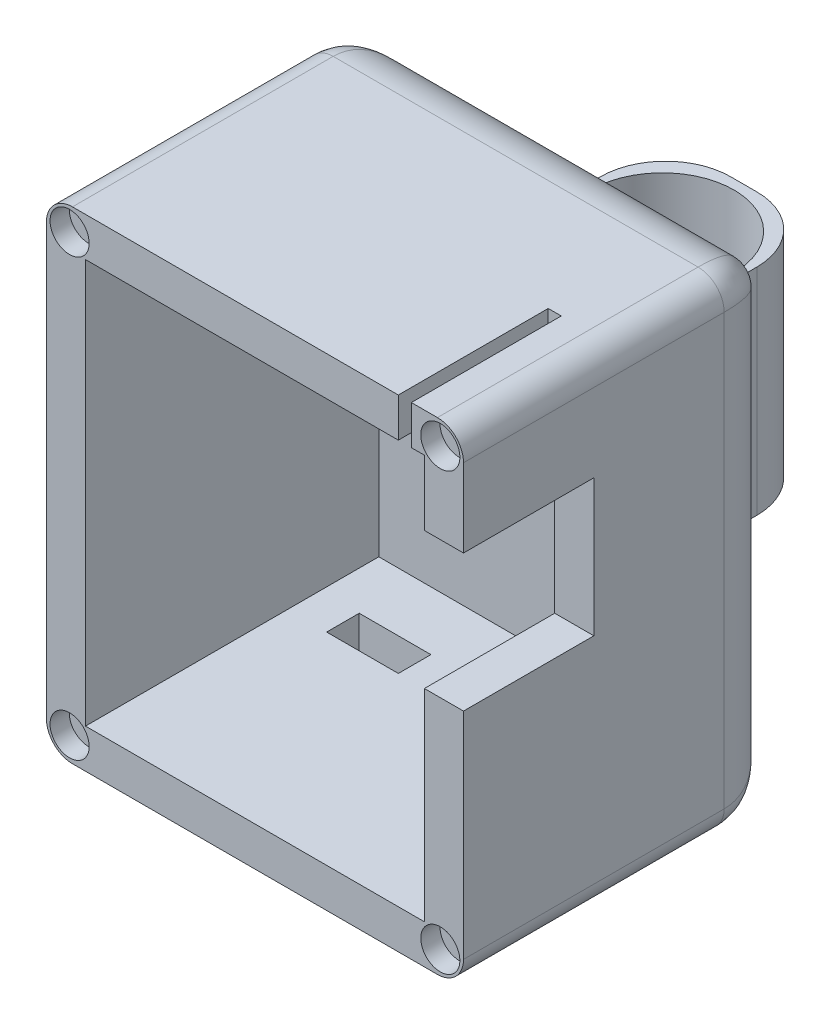
SolidWorks part; units mm, degrees
ref_plane "정면" through (0, 0, 0) normal (0, 0, 1) x (1, 0, 0)
ref_plane "윗면" through (0, 0, 0) normal (0, 1, 0) x (1, 0, 0)
ref_plane "우측면" through (0, 0, 0) normal (1, 0, 0) x (0, 0, -1)
sketch "스케치1" plane through (0, 0, 0) normal (0, 0, 1) x (1, 0, 0)
  line L0 (32, 74) -> (32, 0) construction
  line L1 (0, 0) -> (64, 0)
  line L2 (0, 0) -> (0, 74)
  line L3 (0, 74) -> (64, 74)
  line L4 (64, 0) -> (64, 74)
  line L5 (0, 37) -> (64, 37) construction
  line L6 (0, 74) -> (6, 68) construction
  line L7 (6, 6) -> (58, 6)
  line L8 (6, 6) -> (6, 68)
  line L9 (6, 68) -> (58, 68)
  line L10 (58, 6) -> (58, 68)
  line L11 (64, 74) -> (58, 68) construction
  circle A0 centre (3.5212, 70.4788) radius 3
  circle A1 centre (60.4788, 70.4788) radius 3
  circle A2 centre (60.4788, 3.5212) radius 3
  circle A3 centre (3.5212, 3.5212) radius 3
  point P9 (32, 37)
  dimension "D5" = 6
  dimension "D1" = 64
  dimension "D2" = 74
  dimension "D3" = 52
  dimension "D4" = 62
extrude "보스-돌출4" add sketch "스케치1" along normal blind 50 contours L4 L3 L2 L1
ref_plane "평면1" through (64, 74, 50) normal (1, 0, 0) x (0, 0, -1)
sketch "스케치5" plane through (0, 0, 50) normal (0, 0, 1) x (1, 0, 0)
  line L0 (32, 74) -> (32, 0) construction
  line L1 (0, 74) -> (64, 74) construction
  line L2 (0, 0) -> (64, 0) construction
  line L3 (0, 37) -> (64, 37) construction
  line L4 (0, 0) -> (0, 74) construction
  line L5 (64, 0) -> (64, 74) construction
  line L7 (6, 6) -> (58, 6)
  line L8 (6, 6) -> (6, 68)
  line L9 (6, 68) -> (58, 68)
  line L10 (58, 6) -> (58, 68)
  line L11 (32, 68) -> (32, 6) construction
  line L12 (6, 37) -> (58, 37) construction
  point P12 (32, 37)
  dimension "D1" = 52
  dimension "D2" = 62
extrude "컷-돌출1" cut sketch "스케치5" against normal blind 45
sketch "스케치6" plane through (0, 0, 50) normal (0, 0, 1) x (1, 0, 0)
  line L6 (0, 74) -> (6, 68) construction
  circle A0 centre (3.5581, 70.4419) radius 3
  circle A1 centre (60.4419, 70.4419) radius 3
  circle A2 centre (60.4419, 3.5581) radius 3
  circle A3 centre (3.5581, 3.5581) radius 3
  dimension "D1" = 6
extrude "컷-돌출2" cut sketch "스케치6" against normal blind 2.95 contours A3 | A2 | A1 | A0
sketch "스케치7" plane through (0, 0, 50) normal (0, 0, 1) x (1, 0, 0)
  line L0 (64, 74) -> (56, 74) construction
  line L1 (0, 74) -> (64, 74) construction
  line L3 (56, 74) -> (54, 74)
  dimension "D1" = 8
  dimension "D2" = 2
sketch "스케치8" plane through (0, 74, 0) normal (0, 1, 0) x (1, 0, 0)
  line L0 (54, -50) -> (54, -27)
  line L1 (64, -50) -> (56, -50) construction
  line L2 (54, -50) -> (56, -50)
  line L3 (56, -50) -> (54, -50) construction
  line L4 (56, -50) -> (56, -27)
  line L5 (56, -27) -> (54, -27)
  dimension "D1" = 23
extrude "컷-돌출4" cut sketch "스케치8" against normal blind 8 contours L0 L5 L4 L2
sketch "스케치9" plane through (64, 0, 0) normal (1, 0, 0) x (0, 0, -1)
  line L0 (0, 74) -> (-30, 74) construction
  line L2 (-50, 74) -> (0, 74) construction
  line L3 (-30, 74) -> (-30, 58) construction
  line L5 (-50, 0) -> (-50, 74) construction
  line L6 (-30, 58) -> (-50, 58)
  line L7 (-30, 58) -> (-30, 37)
  line L8 (-30, 37) -> (-50, 37)
  line L9 (-50, 58) -> (-50, 37)
  dimension "D1" = 30
  dimension "D2" = 16
extrude "컷-돌출5" cut sketch "스케치9" against normal blind 8 contours L7 L8 L9 L6
sketch "스케치10" plane through (0, 0, 0) normal (0, -1, 0) x (1, 0, 0)
  line L0 (0, 0) -> (12, 0) construction
  line L1 (0, 0) -> (64, 0) construction
  line L2 (12, 0) -> (12, 19) construction
  line L4 (12, 19) -> (23, 19)
  line L5 (12, 19) -> (12, 14)
  line L6 (12, 14) -> (23, 14)
  line L7 (23, 19) -> (23, 14)
  dimension "D1" = 12
  dimension "D2" = 19
  dimension "D3" = 11
  dimension "D4" = 5
extrude "컷-돌출6" cut sketch "스케치10" against normal blind 8
fillet "필렛1" radius 4 4 edges at (0, 0, 25) (64, 0, 25) (64, 74, 25) (0, 74, 25)
ref_plane "평면3" through (4, 0, 0) normal (1, 0, 0) x (0, 0, -1)
sketch "스케치15" plane through (0, 0, 0) normal (0, 0, -1) x (-1, 0, 0)
  line L0 (-32, 74) -> (-32, 0) construction
  line L1 (-4, 74) -> (-60, 74) construction
  line L2 (-4, 0) -> (-60, 0) construction
  line L3 (0, 37) -> (-64, 37) construction
  line L5 (0, 4) -> (0, 70) construction
  line L6 (-64, 91.6) -> (-64, 56.4) construction
  line L8 (-44, 20.5) -> (-20, 20.5)
  line L9 (-44, 20.5) -> (-44, 53.5)
  line L10 (-44, 53.5) -> (-20, 53.5)
  line L11 (-20, 20.5) -> (-20, 53.5)
  line L12 (-32, 53.5) -> (-32, 20.5) construction
  line L13 (-44, 37) -> (-20, 37) construction
  point P12 (-32, 37)
  dimension "D1" = 24
  dimension "D2" = 33
extrude "보스-돌출7" add sketch "스케치15" along normal blind 25 contours L10 L11 L8 L9
sketch "스케치18" plane through (0, 53.5, 0) normal (0, 1, 0) x (1, 0, 0)
  line L0 (32, 25) -> (32, 0) construction
  line L1 (44, 25) -> (20, 25) construction
  line L2 (44, 0) -> (20, 0) construction
  line L3 (20, 12.5) -> (44, 12.5) construction
  line L4 (20, 25) -> (20, 0) construction
  line L5 (44, 25) -> (44, 0) construction
  circle A0 centre (32, 12.5) radius 11
  dimension "D1" = 22
fillet "필렛3" radius 10 2 edges at (44, 37, -25) (20, 37, -25)
extrude "컷-돌출7" cut sketch "스케치18" against normal through all contours A0
fillet "필렛4" radius 10 8 edges at (62.8284, 1.1716, 0) (64, 37, 0) (62.8284, 72.8284, 0) (32, 74, 0) (1.1716, 72.8284, 0) (0, 37, 0) (1.1716, 1.1716, 0) (32, 0, 0)
